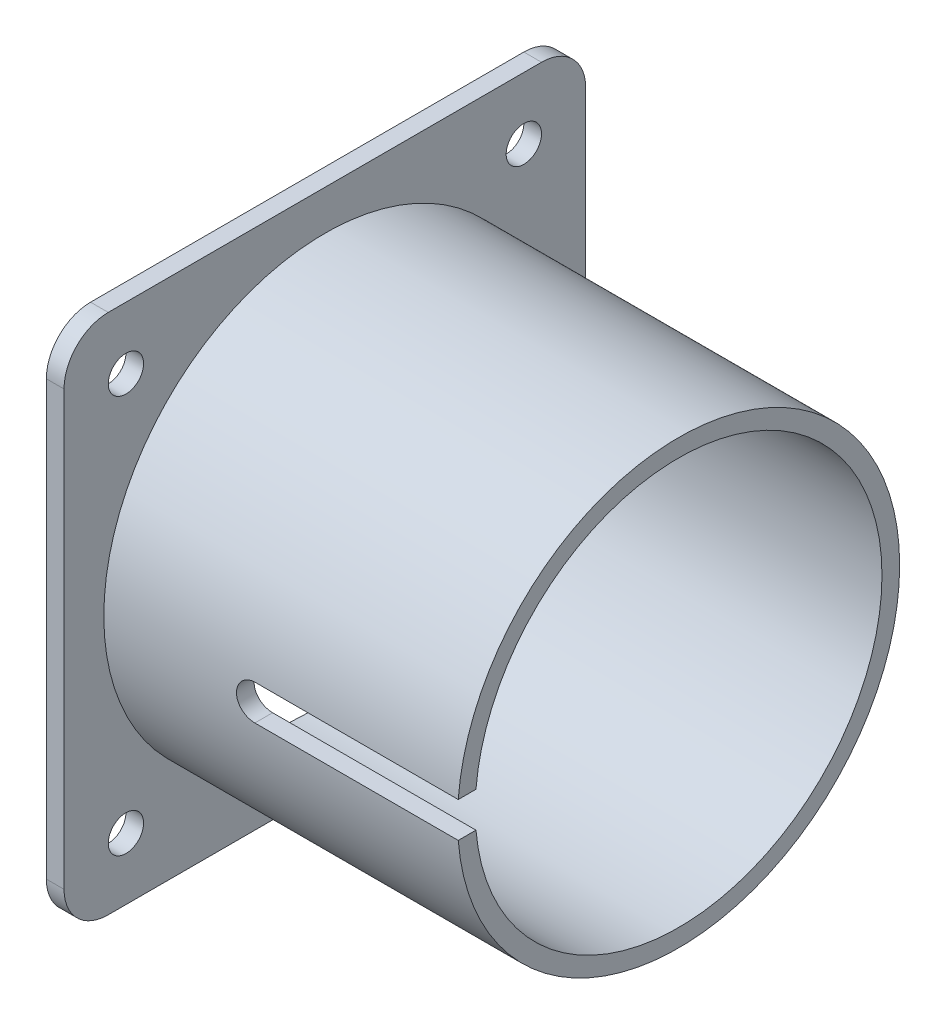
SolidWorks part; units mm, degrees
material "PVC Rígido"
ref_plane "Front" through (0, 0, 0) normal (0, 0, 1) x (1, 0, 0)
ref_plane "Top" through (0, 0, 0) normal (0, 1, 0) x (1, 0, 0)
ref_plane "Right" through (0, 0, 0) normal (1, 0, 0) x (0, 0, -1)
sketch "Croquis1" plane through (0, 0, 0) normal (1, 0, 0) x (0, 0, -1)
  line L0 (0, 0) -> (0, -46) construction
  line L1 (-49, 59) -> (49, 59)
  line L2 (-59, 49) -> (-59, -49)
  line L3 (-49, -59) -> (49, -59)
  line L4 (59, 49) -> (59, -49)
  line L5 (-59, 59) -> (59, -59) construction
  line L6 (-59, -59) -> (59, 59) construction
  line L7 (-45, 45) -> (45, 45)
  line L8 (-45, 45) -> (-45, -45)
  line L9 (-45, -45) -> (45, -45)
  line L10 (45, 45) -> (45, -45)
  line L11 (-45, 45) -> (45, -45) construction
  line L12 (-45, -45) -> (45, 45) construction
  line L13 (0, 0) -> (-45, 0) construction
  line L14 (-45, 45) -> (45, 45)
  circle A0 centre (0, 0) radius 46
  arc A1 (-59, 49) -> (-49, 59) centre (-49, 49) cw
  arc A2 (49, 59) -> (59, 49) centre (49, 49) cw
  arc A3 (59, -49) -> (49, -59) centre (49, -49) cw
  arc A4 (-49, -59) -> (-59, -49) centre (-49, -49) cw
  circle A5 centre (45, -45) radius 4
  circle A6 centre (-45, -45) radius 4
  circle A7 centre (-45, 45) radius 4
  circle A8 centre (45, 45) radius 4
  point P0 (0, 0)
  dimension "D2" = 92
  dimension "D3" = 10
  dimension "D4" = 10
  dimension "D6" = 8
  dimension "D1" = 118
  dimension "D5" = 90
extrude "Saliente-Extruir1" add sketch "Croquis1" along normal blind 4 contours A4 L3 A3 L4 A2 L1 A1 L2 L7 A8 L10 A0 A5 L9 A6 L8 A7 L14 | L8 A6 L9 A0 | A7 L8 A0 L14 | L10 A8 L7 A0 | A5 L10 A0 L9 region at (0, 57.3312, 0) region at (0, 35.4693, 35.4693) region at (0, 35.4693, -35.4693) region at (0, -35.4693, 35.4693) region at (0, -35.4693, -35.4693)
sketch "Croquis2" plane through (4, 0, 0) normal (1, 0, 0) x (0, 0, -1)
  circle A0 centre (0, 0) radius 46
  circle A1 centre (0, 0) radius 50
  dimension "D1" = 100
extrude "Saliente-Extruir2" add sketch "Croquis2" along normal blind 80
ref_plane "Plano1" through (0, 0, 50) normal (0, 0, 1) x (1, 0, 0)
sketch "Croquis3" plane through (0, 0, 50) normal (0, 0, 1) x (1, 0, 0)
  line L0 (84, 0) -> (17.6913, 0) construction
  line L1 (84, -50) -> (84, 50) construction
  line L2 (84, 0) -> (84, 4)
  line L3 (84, 4) -> (38, 4)
  line L4 (84, -4) -> (38, -4)
  line L5 (84, -4) -> (84, 0)
  arc A0 (38, -4) -> (38, 4) centre (38, 0) cw
  dimension "D1" = 8
  dimension "D2" = 46
extrude "Cortar-Extruir1" cut sketch "Croquis3" against normal blind 10
sketch "Croquis4" plane through (0, 0, 0) normal (-1, 0, 0) x (0, 0, 1)
  circle A0 centre (0, 0) radius 50
  circle A1 centre (0, 0) radius 54
  dimension "D1" = 100
  dimension "D2" = 108
extrude "Cortar-Extruir2" cut sketch "Croquis4" against normal blind 3
